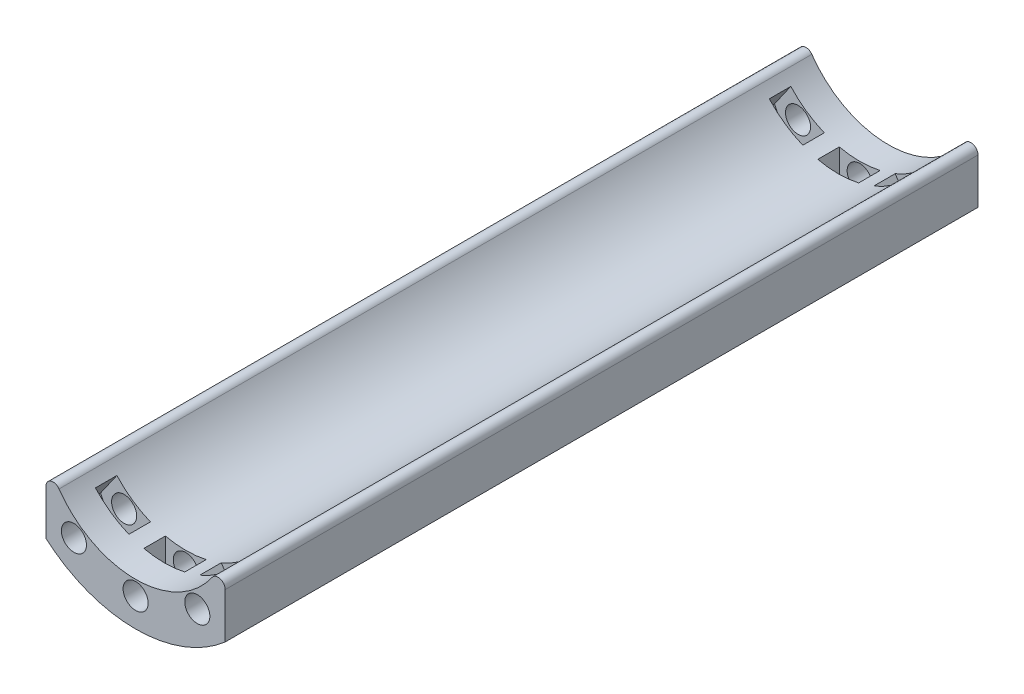
SolidWorks part; units mm, degrees
ref_plane "Front Plane" through (0, 0, 0) normal (0, 0, 1) x (1, 0, 0)
ref_plane "Top Plane" through (0, 0, 0) normal (0, 1, 0) x (1, 0, 0)
ref_plane "Right Plane" through (0, 0, 0) normal (1, 0, 0) x (0, 0, -1)
sketch "Sketch1" plane through (0, 0, 0) normal (0, 0, 1) x (1, 0, 0)
  line L2 (-18.375, -14.3091) -> (-18.375, 159.3091)
  line L3 (-43.375, 159.3091) -> (-43.375, -14.3091)
  line L4 (-18.375, -14.3091) -> (-18.375, 159.3091)
  line L5 (-43.375, 159.3091) -> (-43.375, -14.3091)
  circle A0 centre (-30.875, 0) radius 13
  arc A2 (-18.375, 159.3091) -> (-43.375, 159.3091) centre (-30.875, 145) ccw
  arc A3 (-43.375, -14.3091) -> (-18.375, -14.3091) centre (-30.875, 0) ccw
  arc A4 (-18.375, 159.3091) -> (-43.375, 159.3091) centre (-30.875, 145) ccw
  arc A5 (-43.375, -14.3091) -> (-18.375, -14.3091) centre (-30.875, 0) ccw
  dimension "D2" = 6
  dimension "D1" = 0
extrude "Boss-Extrude1" add sketch "Sketch1" along normal up to surface (105 mm away) contours L5 A5 L4 A0 region at (-30.875, -13.7148, 0)
sketch "Sketch3" plane through (0, 0, 0) normal (0, 0, -1) x (-1, 0, 0)
  circle A1 centre (30.875, -15) radius 1.75 construction
  circle A2 centre (39.4786, -12.2873) radius 1.75 construction
  circle A3 centre (22.2714, -12.2873) radius 1.75
  circle A4 centre (30.875, -15) radius 1.75
  circle A5 centre (39.4786, -12.2873) radius 1.75
  circle A6 centre (22.2714, -12.2873) radius 1.75 construction
  circle A7 centre (22.2714, -12.2873) radius 1.75 construction
  point P9 (0, 0)
  point P11 (0, 0)
  point P12 (0, 0)
  point P13 (0, 0)
  point P14 (0, 0)
  point P15 (0, 0)
  point P16 (0, 0)
extrude "Cut-Extrude1" cut sketch "Sketch3" against normal blind 15 contours A3 | A4 | A5 region at (-22.2714, -12.2873, 0) region at (-30.875, -15, 0) region at (-39.4786, -12.2873, 0)
ref_plane "Plane1" through (0, 0, 4) normal (0, 0, -1) x (-1, 0, 0)
ref_plane "Plane2" through (0, 0, 52.5) normal (0, 0, -1) x (-1, 0, 0)
sketch "Sketch4" plane through (0, 0, 4) normal (0, 0, -1) x (-1, 0, 0)
  line L0 (20.8806, -9.3047) -> (21.2653, -8.7552)
  line L1 (30.875, -18.2909) -> (33.725, -16.6454)
  line L2 (33.725, -16.6454) -> (33.725, -13.3546)
  line L3 (33.725, -13.3546) -> (30.875, -11.7091)
  line L4 (30.875, -11.7091) -> (28.025, -13.3546)
  line L5 (28.025, -13.3546) -> (28.025, -16.6454)
  line L6 (28.025, -16.6454) -> (30.875, -18.2909)
  line L7 (25.5497, -12.5741) -> (25.9345, -12.0246)
  line L8 (24.1589, -9.5915) -> (20.3838, -14.983) construction
  line L9 (20.3838, -14.983) -> (23.6621, -15.2698)
  line L10 (23.6621, -15.2698) -> (25.5497, -12.5741)
  line L11 (25.5497, -12.5741) -> (24.1589, -9.5915)
  line L12 (24.1589, -9.5915) -> (20.8806, -9.3047)
  line L13 (20.8806, -9.3047) -> (18.993, -12.0005)
  line L14 (18.993, -12.0005) -> (20.3838, -14.983)
  line L15 (30.875, 0) -> (24.1589, -9.5915) construction
  line L16 (30.875, 0) -> (30.875, -19) construction
  line L17 (28.025, -13.3546) -> (28.025, -12.6837)
  line L18 (33.725, -13.3546) -> (33.725, -12.6837)
  line L19 (36.2003, -12.5741) -> (37.5911, -9.5915)
  line L20 (37.5911, -9.5915) -> (40.8694, -9.3047)
  line L21 (40.8694, -9.3047) -> (42.757, -12.0005)
  line L22 (42.757, -12.0005) -> (41.3662, -14.983)
  line L23 (41.3662, -14.983) -> (38.0879, -15.2698)
  line L24 (38.0879, -15.2698) -> (36.2003, -12.5741)
  line L25 (36.2003, -12.5741) -> (35.8155, -12.0246)
  line L26 (40.8694, -9.3047) -> (40.4847, -8.7552)
  line L27 (18.375, -14.3091) -> (18.375, -3.5707) construction
  line L28 (18.375, -14.3091) -> (18.375, -3.5707)
  line L29 (43.375, -3.5707) -> (43.375, -14.3091) construction
  line L30 (43.375, -3.5707) -> (43.375, -14.3091)
  circle A0 centre (30.875, -15) radius 2.85 construction
  arc A1 (18.375, -14.3091) -> (43.375, -14.3091) centre (30.875, 0) ccw construction
  arc A2 (18.375, -14.3091) -> (43.375, -14.3091) centre (30.875, 0) ccw
  arc A3 (18.375, -3.5707) -> (43.375, -3.5707) centre (30.875, 0) ccw construction
  arc A4 (18.375, -3.5707) -> (43.375, -3.5707) centre (30.875, 0) ccw
  circle A5 centre (22.2714, -12.2873) radius 2.85 construction
  circle A6 centre (22.2714, -12.2873) radius 1.75 construction
  circle A7 centre (30.875, -15) radius 1.75 construction
  dimension "D1" = 5.7
extrude "Cut-Extrude2" cut sketch "Sketch4" against normal blind 3 contours A4 L12 L13 L14 A2 L9 L10 L11 | A4 L0 L12 | A4 L11 L7 | A4 L4 L5 L6 A2 L1 L2 L3 | A4 L17 L4 | A4 L3 L18 | A4 L19 L24 L23 A2 L22 L21 L20 | A4 L25 L19 | A4 L20 L26 region at (-21.3409, -9.1521, 4) region at (-22.1244, -12.4971, 4) region at (-25.5357, -12.0894, 4) region at (-28.3145, -12.9655, 4) region at (-30.875, -15.2561, 4) region at (-40.4091, -9.1521, 4) region at (-33.4355, -12.9655, 4) region at (-39.6256, -12.4971, 4) region at (-36.2143, -12.0894, 4)
mirror "Mirror1" about plane through (0, 0, 52.5) normal (0, 0, -1) of "Cut-Extrude1", "Cut-Extrude2"
fillet "Fillet1" radius 1 2 edges at (-43.375, -3.5707, 52.5) (-18.375, -3.5707, 52.5)
ref_plane "Plane3" through (0, -19, 0) normal (0, -1, 0) x (-1, 0, 0)
